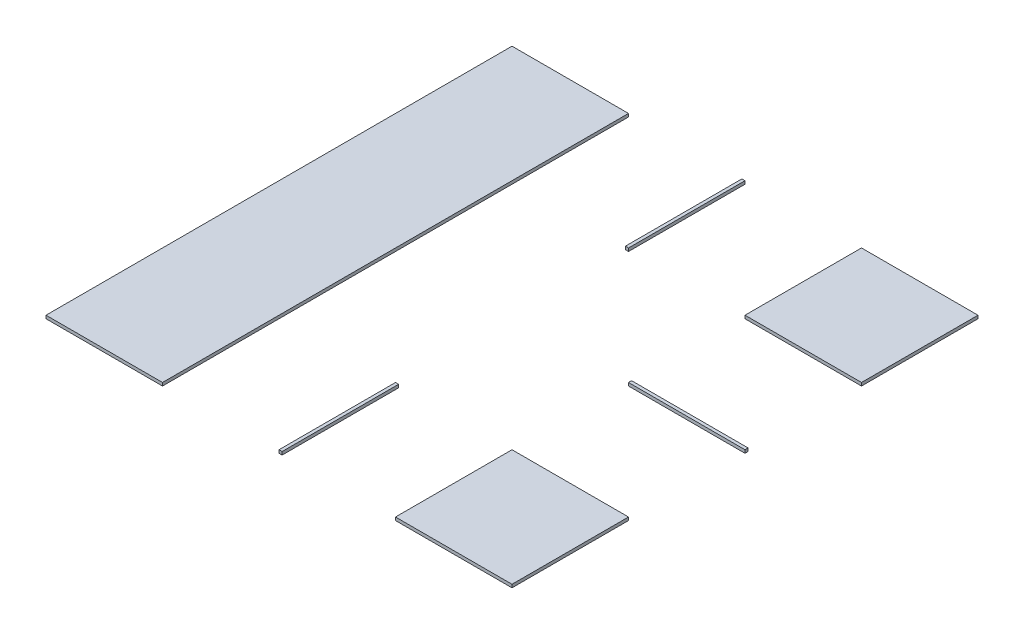
SolidWorks part; units mm, degrees
ref_plane "Front Plane" through (0, 0, 0) normal (0, 0, 1) x (1, 0, 0)
ref_plane "Top Plane" through (0, 0, 0) normal (0, 1, 0) x (1, 0, 0)
ref_plane "Right Plane" through (0, 0, 0) normal (1, 0, 0) x (0, 0, -1)
sketch "Sketch1" plane through (0, 0, 0) normal (0, 1, 0) x (1, 0, 0)
  line L0 (375, -375) -> (750, -750) construction
  line L1 (-750, -750) -> (750, -750)
  line L2 (-750, -750) -> (-750, 750)
  line L3 (-750, 750) -> (750, 750)
  line L4 (750, -750) -> (750, 750)
  line L5 (-750, -750) -> (-375, -375) construction
  line L6 (-750, 750) -> (-375, 375) construction
  line L7 (-375, -750) -> (375, -750)
  line L8 (-375, -750) -> (-375, 750)
  line L9 (-375, 750) -> (375, 750)
  line L10 (375, -750) -> (375, -375)
  line L20 (-750, 442.3995) -> (-750, -307.6005)
  line L27 (375, 375) -> (750, 375)
  line L28 (-750, 375) -> (-750, -375)
  line L29 (375, -375) -> (750, -375)
  line L30 (750, 375) -> (750, -375)
  line L31 (375, 375) -> (750, 750) construction
  line L32 (375, 375) -> (375, 750)
  point P0 (0, 0)
  point P10 (750, 0)
  point P11 (0, 750)
  dimension "D1" = 1500
  dimension "D2" = 750
extrude "Boss-Extrude1" add sketch "Sketch1" along normal blind 10 contours L1 L8 L3 L2 L20 | L32 L27 L4 L3 | L29 L10 L1 L4 region at (-562.5, 0, 0) region at (562.5, 0, 562.5) region at (562.5, 0, -562.5)
sketch "Sketch2" plane through (0, 0, 0) normal (0, 1, 0) x (1, 0, 0)
  line L4 (0, 750) -> (0, 375)
  line L8 (0, -750) -> (0, -375)
  line L11 (750, 0) -> (375, 0)
  dimension "D1" = 375
  dimension "D4" = 375
  dimension "D6" = 375
extrude "Extrude-Thin1" add sketch "Sketch2" along normal blind 10 separate body thin thin type one direction wall 10
equation "\"Scale\"= 8"
equation "\"Tile Size\"= \"Road Size\" * 2"
equation "\"D1@Sketch1\"=\"Tile Size\""
equation "\"Road Size\"= \"Real Lane Size\" * 2 / \"Scale\""
equation "\"D2@Sketch1\"=\"Road Size\""
equation "\"Real Lane Size\"= 3m"
